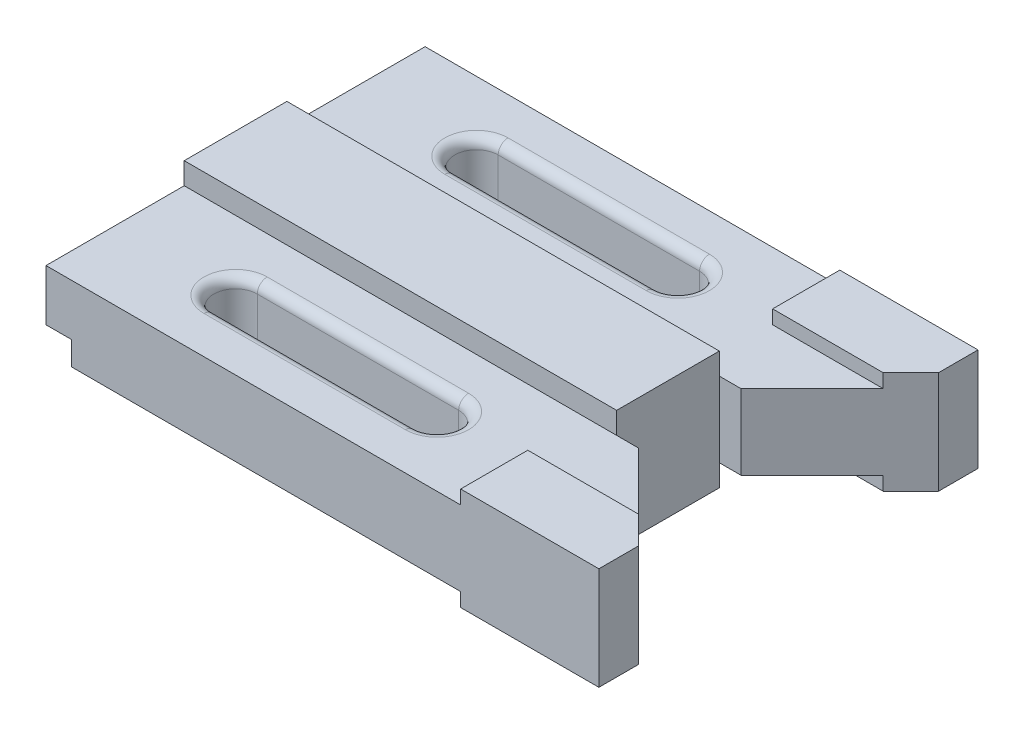
SolidWorks part; units mm, degrees
material "1060 Alloy"
ref_plane "Front Plane" through (0, 0, 0) normal (0, 0, 1) x (1, 0, 0)
ref_plane "Top Plane" through (0, 0, 0) normal (0, 1, 0) x (1, 0, 0)
ref_plane "Right Plane" through (0, 0, 0) normal (1, 0, 0) x (0, 0, -1)
sketch "Sketch1" plane through (0, 0, 0) normal (0, 1, 0) x (1, 0, 0)
  line L0 (0, 0) -> (140, 0)
  line L1 (140, 0) -> (140, 10)
  line L2 (140, 10) -> (115, 35)
  line L4 (109.5, 35) -> (109.5, 48)
  line L6 (0, 96) -> (0, 0)
  line L7 (105, 0) -> (105, 17)
  line L8 (105, 17) -> (133, 17)
  line L9 (115, 35) -> (109.5, 35)
  line L10 (115, 61) -> (109.5, 61)
  line L11 (30.5, 17.5) -> (81.5, 17.5) construction
  line L12 (30.5, 23) -> (81.5, 23)
  line L13 (30.5, 12) -> (81.5, 12)
  line L14 (0, 48) -> (109.5, 48) construction
  line L15 (30.5, 78.5) -> (81.5, 78.5) construction
  line L16 (30.5, 73) -> (81.5, 73)
  line L17 (30.5, 84) -> (81.5, 84)
  line L18 (105, 79) -> (133, 79)
  line L19 (105, 96) -> (105, 79)
  line L20 (0, 96) -> (140, 96)
  line L21 (140, 96) -> (140, 86)
  line L22 (140, 86) -> (115, 61)
  line L23 (109.5, 61) -> (109.5, 48)
  line L24 (109.5, 61) -> (0, 61)
  line L25 (109.5, 35) -> (0, 35)
  arc A0 (30.5, 23) -> (30.5, 12) centre (30.5, 17.5) ccw
  arc A1 (81.5, 12) -> (81.5, 23) centre (81.5, 17.5) ccw
  arc A2 (30.5, 73) -> (30.5, 84) centre (30.5, 78.5) cw
  arc A3 (81.5, 84) -> (81.5, 73) centre (81.5, 78.5) cw
  point P11 (109.5, 41.5)
  point P16 (56, 17.5)
  point P24 (56, 78.5)
  dimension "D12" = 5.5
  dimension "D2" = 10
  dimension "D3" = 31.5
  dimension "D4" = 17
  dimension "D5" = 17.5
  dimension "D6" = 35
  dimension "D7" = 35
  dimension "D8" = 30.5
  dimension "D9" = 45
  dimension "D10" = 30.5
  dimension "D11" = 51
  dimension "D13" = 109.5
  dimension "D14" = 140
extrude "Boss-Extrude3" add sketch "Sketch1" along normal mid plane 30 contours L25 L4 L23 L24 L6 region at (54.75, 0, -48)
extrude "Boss-Extrude4" add sketch "Sketch1<7>" along normal mid plane 19 contours L9 L25 L6 L0 L7 L8 L2 A1 L13 A0 L12 | L24 L10 L22 L18 L19 L20 L6 L17 A3 L16 A2 region at (1.3753, 0, -17.5) region at (1.3753, 0, -78.5)
sketch "Sketch1<7>" plane through (0, 0, 0) normal (0, 1, 0) x (1, 0, 0) same geometry as "Sketch1"
extrude "Boss-Extrude5" add sketch "Sketch1<8>" along normal mid plane 26 contours L8 L7 L0 L1 L2 | L22 L21 L20 L19 L18 region at (121.8487, 0, -8.2352) region at (121.8487, 0, -87.7648)
sketch "Sketch1<8>" plane through (0, 0, 0) normal (0, 1, 0) x (1, 0, 0) same geometry as "Sketch1"
fillet "Fillet2" radius 2.5 8 edges at (56, 9.5, -12) (56, -9.5, -12) (56, 9.5, -23) (56, -9.5, -23) (25, 9.5, -17.5) (25, -9.5, -17.5) (87, 9.5, -17.5) (87, -9.5, -17.5)
fillet "Fillet3" radius 2.5 8 edges at (56, 9.5, -84) (56, -9.5, -84) (56, 9.5, -73) (56, -9.5, -73) (87, 9.5, -78.5) (87, -9.5, -78.5) (25, 9.5, -78.5) (25, -9.5, -78.5)
sketch "Sketch2" plane through (0, 0, 0) normal (0, 0, 1) x (1, 0, 0)
  line L4 (0, -15) -> (6.5, -15)
  line L5 (0, -15) -> (0, -3.5)
  line L6 (0, -3.5) -> (6.5, -3.5)
  line L7 (6.5, -15) -> (6.5, -3.5)
  dimension "D1" = 11.5
  dimension "D2" = 6.5
extrude "Cut-Extrude1" cut sketch "Sketch2" against normal through all
equation "\"A\"= 140mm"
equation "\"B\"= 51mm"
